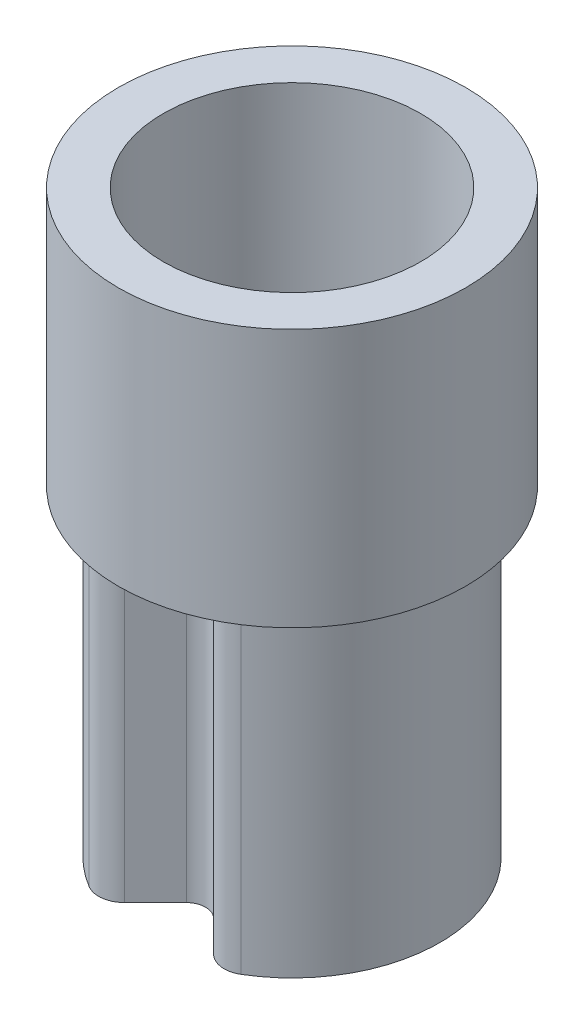
SolidWorks part; units mm, degrees
ref_plane "Front Plane" through (0, 0, 0) normal (0, 0, 1) x (1, 0, 0)
ref_plane "Top Plane" through (0, 0, 0) normal (0, 1, 0) x (1, 0, 0)
ref_plane "Right Plane" through (0, 0, 0) normal (1, 0, 0) x (0, 0, -1)
sketch "Sketch1" plane through (0, 0, 0) normal (0, 1, 0) x (1, 0, 0)
  line L0 (0, 0) -> (0, -1.15) construction
  line L1 (-0.4488, -1.0588) -> (-0.1061, -0.7161)
  line L2 (0.1061, -0.7161) -> (0.4488, -1.0588)
  line L3 (-0.4796, -0.8775) -> (-0.2121, -0.61)
  line L4 (0.2121, -0.61) -> (0.4796, -0.8775)
  arc A0 (0.4488, -1.0588) -> (-0.4488, -1.0588) centre (0, 0) ccw
  arc A1 (0.1061, -0.7161) -> (-0.1061, -0.7161) centre (0, -0.8221) ccw
  arc A2 (0.2121, -0.61) -> (-0.2121, -0.61) centre (0, -0.8221) ccw
  arc A3 (0.4796, -0.8775) -> (-0.4796, -0.8775) centre (0, 0) ccw
  point P8 (0, -0.61)
  dimension "D1" = 2.3
  dimension "D3" = 0.15
  dimension "D2" = 0.61
  dimension "D4" = 0.15
extrude "Boss-Extrude1" add sketch "Sketch1" along normal blind 2.5
fillet "Fillet1" radius 0.05 2 edges at (0.4796, 1.25, 0.8775) (-0.4796, 1.25, 0.8775)
fillet "Fillet2" radius 0.2 2 edges at (0.4488, 1.25, 1.0588) (-0.4488, 1.25, 1.0588)
sketch "Sketch2" plane through (0, 2.5, 0) normal (0, 1, 0) x (1, 0, 0)
  circle A0 centre (0, 0) radius 1.35
  circle A1 centre (0, 0) radius 1
  arc A2 (0.5136, -0.858) -> (-0.5136, -0.858) centre (0, 0) ccw construction
  dimension "D1" = 2.7
extrude "Boss-Extrude2" add sketch "Sketch2" along normal offset from surface (2.01 mm away) 4.51 up to face at (0, 0, 0.537)
